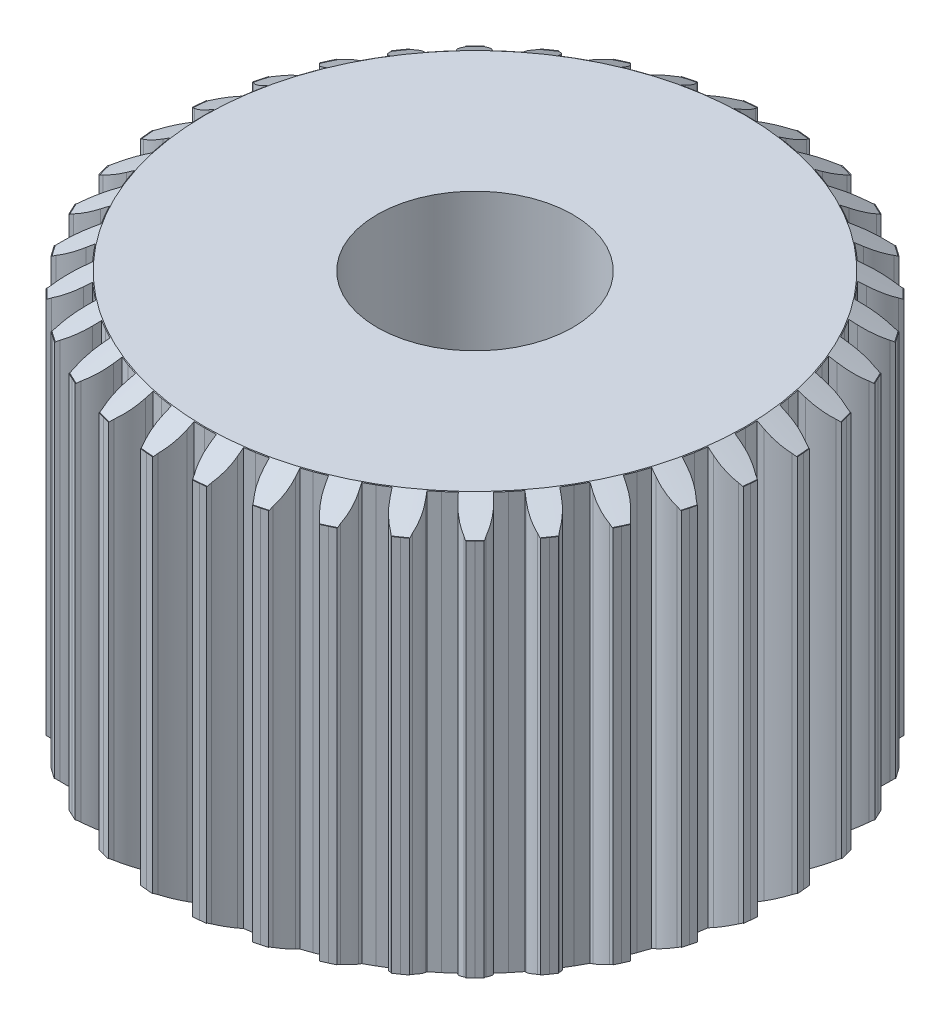
SolidWorks part; units mm, degrees
material "ABS"
ref_plane "Front Plane" through (0, 0, 0) normal (0, 0, 1) x (1, 0, 0)
ref_plane "Top Plane" through (0, 0, 0) normal (0, 1, 0) x (1, 0, 0)
ref_plane "Right Plane" through (0, 0, 0) normal (1, 0, 0) x (0, 0, -1)
sketch "Sketch1" plane through (0, 0, 0) normal (0, 1, 0) x (1, 0, 0)
  line L0 (0, 0) -> (2.325, 0) construction
  line L1 (0, 0) -> (2.3162, 0.2026) construction
  line L2 (0, 0) -> (2.073, 0.0905) construction
  line L3 (2.075, 0) -> (0, 0)
  line L4 (0, 0) -> (2.0435, 0.3603)
  line L5 (2.073, 0.0905) -> (2.075, 0)
  line L6 (2.0558, 0.2815) -> (2.0435, 0.3603)
  line L7 (2.073, 0.0905) -> (2.123, 0.0927)
  line L8 (2.2918, 0.14) -> (2.32, 0.1528)
  line L9 (2.0558, 0.2815) -> (2.1056, 0.2858)
  line L10 (2.2813, 0.2601) -> (2.3113, 0.2524)
  line L11 (2.3113, 0.2524) -> (2.3162, 0.2026)
  line L12 (2.3162, 0.2026) -> (2.32, 0.1528)
  circle A0 centre (0, 0) radius 2.325 construction
  circle A1 centre (0, 0) radius 2.075 construction
  arc A4 (2.123, 0.0927) -> (2.2918, 0.14) centre (2.1062, 0.4772) ccw
  arc A5 (2.1056, 0.2858) -> (2.2813, 0.2601) centre (2.1392, -0.0976) cw
  dimension "D1" = 4.65
  dimension "D2" = 4.15
  dimension "D3" = 5
  dimension "D4" = 2.5
  dimension "D5" = 0.05
  dimension "D6" = 0.05
  dimension "D7" = 0.03
  dimension "D8" = 0.05
  dimension "D9" = 110
  dimension "D10" = 110
extrude "Boss-Extrude1" add sketch "Sketch1" along normal blind 3.2
pattern_circular "CirPattern1" count 36 over 360 about axis through (0, 3.2, 0) along (0, -1, 0) of "Boss-Extrude1"
sketch "Sketch2" plane through (0, 0, 0) normal (0, -1, 0) x (1, 0, 0)
  circle A0 centre (0, 0) radius 0.75
  dimension "D1" = 1.5
extrude "Cut-Extrude1" cut sketch "Sketch2" against normal blind 1
sketch "Sketch3" plane through (0, 0, 0) normal (0, 0, 1) x (1, 0, 0)
  line L0 (-2.37, 0.15) -> (-2.32, 0.15)
  line L1 (-2.32, 3.05) -> (-2.07, 3.2)
  line L2 (-2.024, 3.2) -> (-2.2014, 3.2) construction
  line L3 (-2.37, 3.2) -> (-2.07, 3.2)
  line L4 (-2.07, 0) -> (-2.37, 0)
  line L5 (-2.2014, 0) -> (-2.024, 0) construction
  line L6 (-2.07, 0) -> (-2.32, 0.15)
  line L7 (-2.32, 3.2) -> (-2.32, 0) construction
  line L9 (-2.37, 0.15) -> (-2.37, 0)
  line L10 (-2.37, 3.2) -> (-2.37, 3.05)
  line L11 (-2.37, 3.05) -> (-2.32, 3.05)
  dimension "D1" = 0.3
  dimension "D2" = 0.15
  dimension "D3" = 0.3
  dimension "D4" = 0.15
ref_axis "Axis1" through (0, 0, 0) along (0, 1, 0)
revolve "Cut-Revolve1" cut sketch "Sketch3" angle 360 about axis through (0, 0, 0) along (0, 1, 0)
sketch "Sketch4" plane through (0, 3.2, 0) normal (0, 1, 0) x (1, 0, 0)
  circle A0 centre (0, 0) radius 0.75
  dimension "D1" = 1.5
extrude "Cut-Extrude2" cut sketch "Sketch4" against normal up to surface (3.2 mm away) up to face at (0, 0, -0.75)
